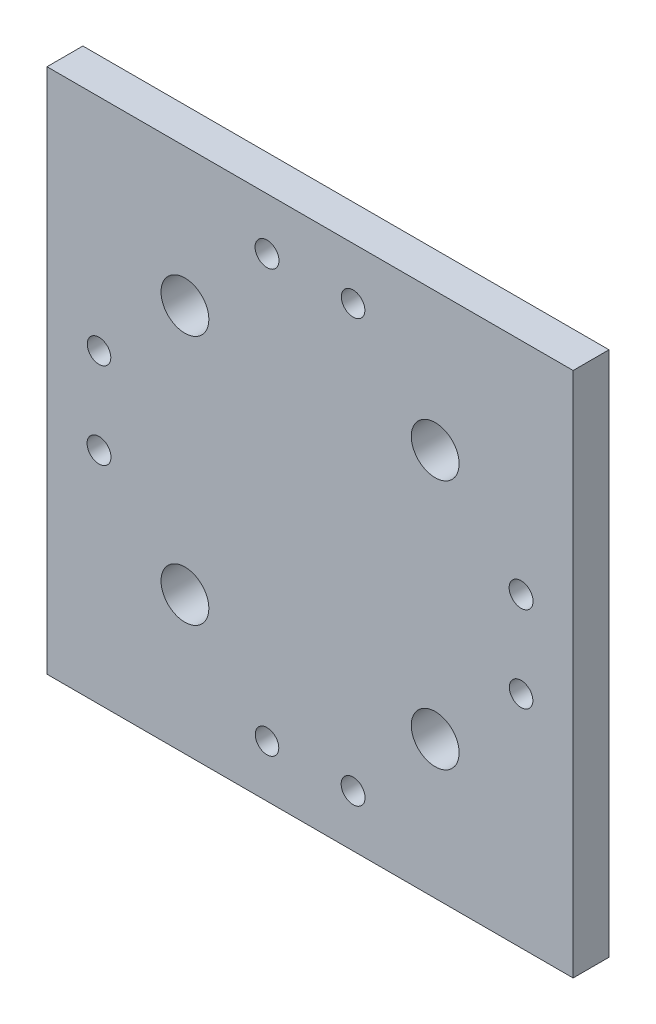
SolidWorks part; units mm, degrees
ref_plane "Front Plane" through (0, 0, 0) normal (0, 0, 1) x (1, 0, 0)
ref_plane "Top Plane" through (0, 0, 0) normal (0, 1, 0) x (1, 0, 0)
ref_plane "Right Plane" through (0, 0, 0) normal (1, 0, 0) x (0, 0, -1)
sketch "Sketch1" plane through (0, 0, 0) normal (0, 0, 1) x (1, 0, 0)
  line L1 (-69.85, -69.85) -> (69.85, -69.85)
  line L2 (-69.85, -69.85) -> (-69.85, 69.85)
  line L3 (-69.85, 69.85) -> (69.85, 69.85)
  line L4 (69.85, -69.85) -> (69.85, 69.85)
  line L5 (-69.85, -69.85) -> (69.85, 69.85) construction
  line L6 (-69.85, 69.85) -> (69.85, -69.85) construction
  point P0 (0, 0)
extrude "Extrude1" add sketch "Sketch1" along normal blind 9.525
sketch "Sketch2" plane through (0, 0, 9.525) normal (0, 0, 1) x (1, 0, 0)
  line L0 (0, 0) -> (-33.2269, 33.2269) construction
  line L1 (0, 0) -> (-56.0324, 0) construction
  line L2 (-56.0324, 0) -> (-56.0324, 11.43) construction
  line L3 (-56.0324, 0) -> (-56.0324, -11.43) construction
hole_wizard "1/2 (0.5) Diameter Hole1" positions "3DSketch1" profile "Sketch3" hole size "1/2" standard "Ansi Inch" end condition through all
sketch3d "3DSketch1"
  point P0 (-33.2269, 33.2269, 9.525)
sketch "Sketch3" plane through (-33.2269, 33.2269, 9.525) normal (1, 0, 0) x (0, -1, 0)
  line L0 (0, 0) -> (0, 9.525)
  line L1 (0, 9.525) -> (6.35, 9.525)
  line L2 (6.35, 9.525) -> (6.35, 0)
  line L5 (6.35, 0) -> (0, 0)
  line L11 (0, -6.35) -> (0, 107.95) construction
  dimension "Thru Hole Dia." = 12.7
  dimension "Thru Hole Depth" = 9.525
hole_wizard "D (0.246) Diameter Hole1" positions "3DSketch2" profile "Sketch4" hole size "D" standard "Ansi Inch"
sketch3d "3DSketch2"
  point P3 (-56.0324, 11.43, 9.525)
sketch "Sketch4" plane through (-56.0324, 11.43, 9.525) normal (1, 0, 0) x (0, -1, 0)
  line L0 (0, 0) -> (0, 35.6592)
  line L1 (0, 35.6592) -> (3.1242, 33.782)
  line L2 (3.1242, 33.782) -> (3.1242, 0)
  line L5 (3.1242, 0) -> (0, 0)
  line L10 (0, 35.6592) -> (-3.1242, 33.782) construction
  line L11 (0, -6.35) -> (0, 107.95) construction
  dimension "Hole Dia." = 6.2484
  dimension "Hole Depth" = 33.782
  dimension "Drill Angle" = 118
hole_wizard "1/4 (0.25) Diameter Hole1" positions "3DSketch3" profile "Sketch5" hole size "1/4" standard "Ansi Inch"
sketch3d "3DSketch3"
  point P0 (-56.0324, -11.43, 9.525)
sketch "Sketch5" plane through (-56.0324, -11.43, 9.525) normal (1, 0, 0) x (0, -1, 0)
  line L0 (0, 0) -> (0, 35.6897)
  line L1 (0, 35.6897) -> (3.175, 33.782)
  line L2 (3.175, 33.782) -> (3.175, 0)
  line L5 (3.175, 0) -> (0, 0)
  line L10 (0, 35.6897) -> (-3.175, 33.782) construction
  line L11 (0, -6.35) -> (0, 107.95) construction
  dimension "Hole Dia." = 6.35
  dimension "Hole Depth" = 33.782
  dimension "Drill Angle" = 118
ref_axis "Axis1" through (0, 0, -0.9525) along (0, 0, 1)
pattern_circular "CirPattern1" count 4 over 360 about axis through (0, 0, -0.9525) along (0, 0, 1) of "1/2 (0.5) Diameter Hole1", "D (0.246) Diameter Hole1", "1/4 (0.25) Diameter Hole1"
ref_plane "Plane1" through (0, 0, 60.325) normal (0, 0, 1) x (1, 0, 0)
sketch "Sketch6" plane through (0, 0, 60.325) normal (0, 0, 1) x (1, 0, 0)
  line L0 (0, 0) -> (0, 69.85) construction
  line L1 (0, 69.85) -> (-69.85, 69.85) construction
